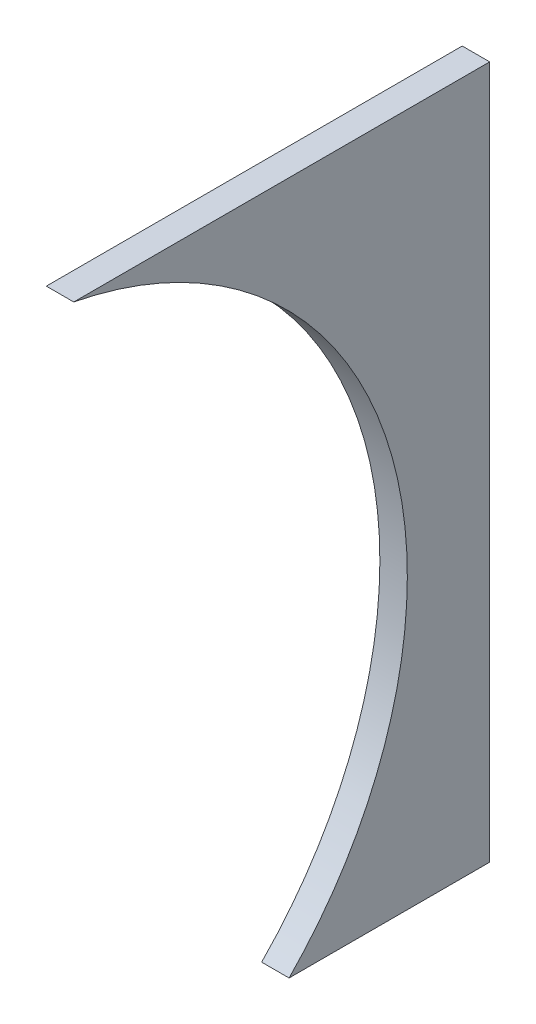
SolidWorks part; units mm, degrees
ref_plane "Front Plane" through (0, 0, 0) normal (0, 0, 1) x (1, 0, 0)
ref_plane "Top Plane" through (0, 0, 0) normal (0, 1, 0) x (1, 0, 0)
ref_plane "Right Plane" through (0, 0, 0) normal (1, 0, 0) x (0, 0, -1)
sketch "Sketch1" plane through (0, 0, 0) normal (1, 0, 0) x (0, 0, -1)
  line L0 (-95.25, 26.7186) -> (133.35, 26.7186) construction
  line L1 (-95.25, -133.5928) -> (133.35, -133.5928)
  line L2 (-95.25, -133.5928) -> (-95.25, 187.0299)
  line L3 (-95.25, 187.0299) -> (133.35, 187.0299)
  line L4 (133.35, -133.5928) -> (133.35, 187.0299)
  line L5 (-95.25, -133.5928) -> (133.35, 187.0299) construction
  line L6 (-95.25, 187.0299) -> (133.35, -133.5928) construction
  point P0 (0, 0)
  dimension "D1" = 228.6
extrude "Boss-Extrude1" add sketch "Sketch1" along normal blind 12.7
sketch "Sketch2" plane through (12.7, 0, 0) normal (1, 0, 0) x (0, 0, -1)
  line L0 (-95.25, 187.0299) -> (-95.25, -133.5928) construction
  circle A0 centre (-95.25, 0) radius 190.5
  dimension "D1" = 381
  dimension "D2" = 0
extrude "Cut-Extrude1" cut sketch "Sketch2" against normal through all
